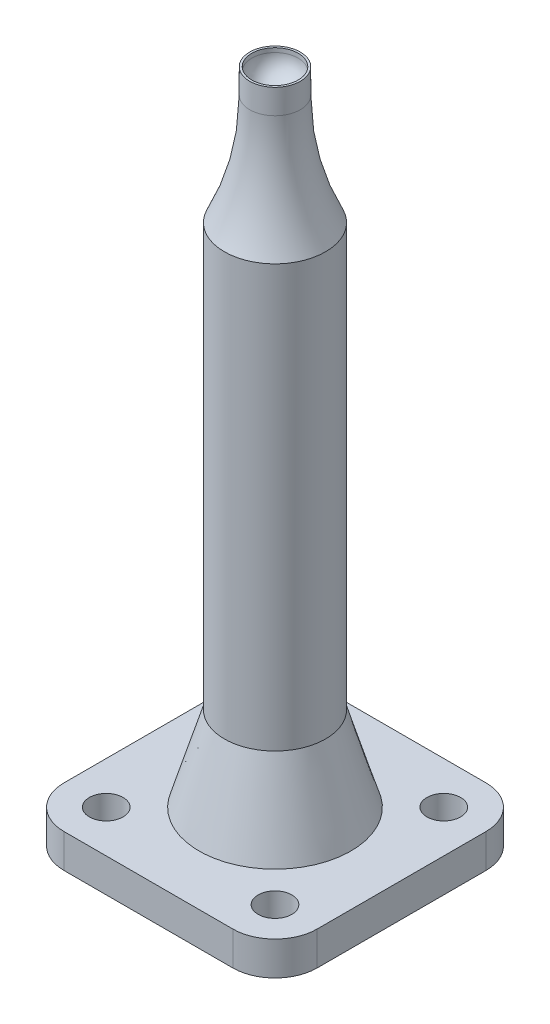
SolidWorks part; units mm, degrees
ref_plane "Спереди" through (0, 0, 0) normal (0, 0, 1) x (1, 0, 0)
ref_plane "Сверху" through (0, 0, 0) normal (0, 1, 0) x (1, 0, 0)
ref_plane "Справа" through (0, 0, 0) normal (1, 0, 0) x (0, 0, -1)
sketch "Эскиз1" plane through (0, 0, 0) normal (0, 1, 0) x (1, 0, 0)
  line L1 (-15, -15) -> (15, -15)
  line L2 (-15, -15) -> (-15, 15)
  line L3 (-15, 15) -> (15, 15)
  line L4 (15, -15) -> (15, 15)
  line L5 (0, 15) -> (0, -15) construction
  line L6 (-15, 0) -> (15, 0) construction
  line L7 (-10, -10) -> (10, -10) construction
  line L8 (-10, -10) -> (-10, 10) construction
  line L9 (-10, 10) -> (10, 10) construction
  line L10 (10, -10) -> (10, 10) construction
  line L11 (0, 10) -> (0, -10) construction
  line L12 (-10, 0) -> (10, 0) construction
  circle A0 centre (-10, 10) radius 2
  circle A1 centre (10, 10) radius 2
  circle A2 centre (10, -10) radius 2
  circle A3 centre (-10, -10) radius 2
  point P0 (0, 0)
  point P4 (0, 0)
  dimension "D5" = 4
  dimension "D1" = 30
  dimension "D2" = 30
  dimension "D3" = 20
  dimension "D4" = 20
extrude "Бобышка-Вытянуть1" add sketch "Эскиз1" along normal blind 4
fillet "Скругление1" radius 5 4 edges at (15, 2, 15) (-15, 2, -15) (15, 2, -15) (-15, 2, 15)
sketch "Эскиз2" plane through (0, 4, 0) normal (0, 1, 0) x (1, 0, 0)
  circle A0 centre (0, 0) radius 6
  dimension "D1" = 12
extrude "Бобышка-Вытянуть2" add sketch "Эскиз2" along normal blind 60
sketch "Эскиз3" plane through (0, 64, 0) normal (0, 1, 0) x (1, 0, 0)
  circle A0 centre (0, 0) radius 3
  dimension "D1" = 6
extrude "Бобышка-Вытянуть3" add sketch "Эскиз3" along normal blind 16
fillet "Скругление2" radius 30 1 edges at (0, 64, 3)
sketch "Эскиз4" plane through (0, 80, 0) normal (0, 1, 0) x (1, 0, 0)
  circle A0 centre (0, 0) radius 2.75
  dimension "D1" = 5.5
extrude "Вырез-Вытянуть1" cut sketch "Эскиз4" against normal blind 3
fillet "Скругление3" radius 2.5 1 edges at (0, 77, 2.75)
fillet "Скругление4" radius 3 1 edges at (0, 4, 6) profile chamfer first distance on face at (0, 4, 6)
